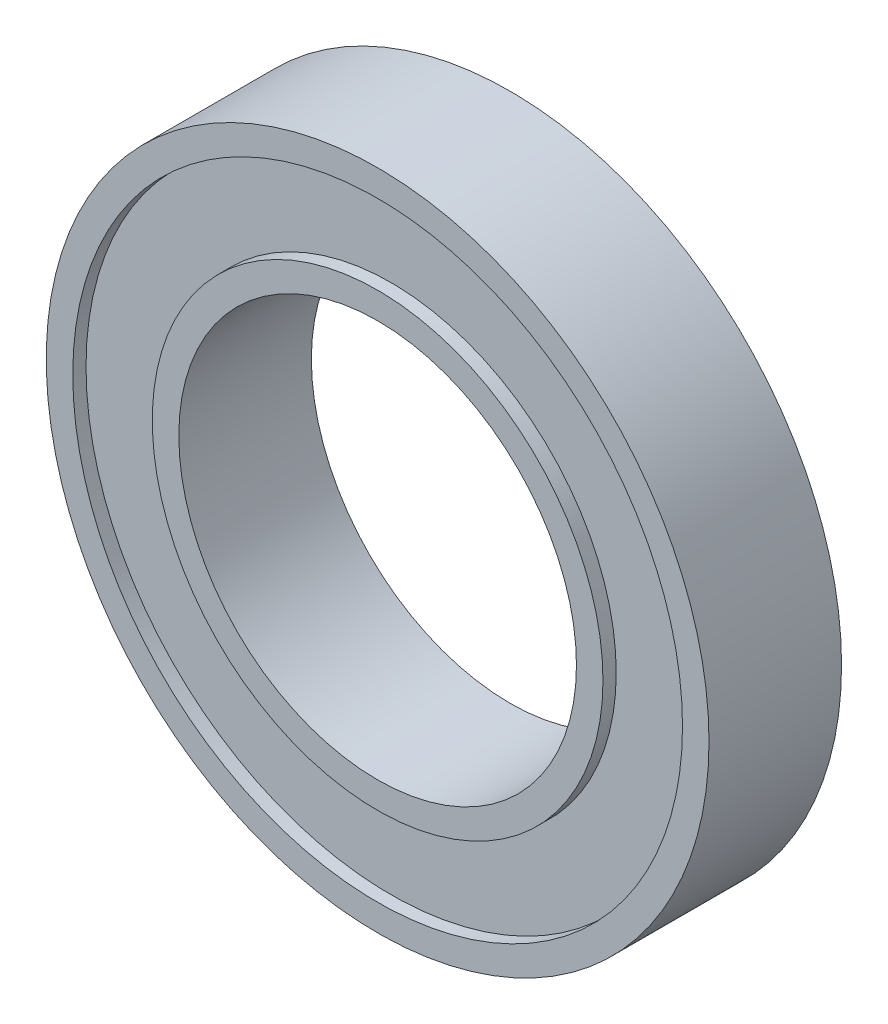
SolidWorks part; units mm, degrees
ref_plane "Alzado" through (0, 0, 0) normal (0, 0, 1) x (1, 0, 0)
ref_plane "Planta" through (0, 0, 0) normal (0, 1, 0) x (1, 0, 0)
ref_plane "Vista lateral" through (0, 0, 0) normal (1, 0, 0) x (0, 0, -1)
sketch "Croquis1" plane through (0, 0, 0) normal (0, 0, 1) x (1, 0, 0)
  circle A0 centre (0, 0) radius 15
  circle A1 centre (0, 0) radius 25
  circle A2 centre (0, 0) radius 23
  circle A3 centre (0, 0) radius 17
  dimension "D1" = 30
  dimension "D2" = 50
  dimension "D3" = 2
  dimension "D4" = 2
extrude "Saliente-Extruir1" add sketch "Croquis1" along normal blind 5 and the other way blind 5 contours A3 A0 | A1 A2 region at (-24.2929, 0, 0) region at (-16.5192, 0, 0)
extrude "Saliente-Extruir2" add sketch "Croquis1<3>" along normal blind 4 and the other way blind 4 contours A2 A3 region at (-22.3495, 0, 0)
sketch "Croquis1<3>" plane through (0, 0, 0) normal (0, 0, 1) x (1, 0, 0) same geometry as "Croquis1"
